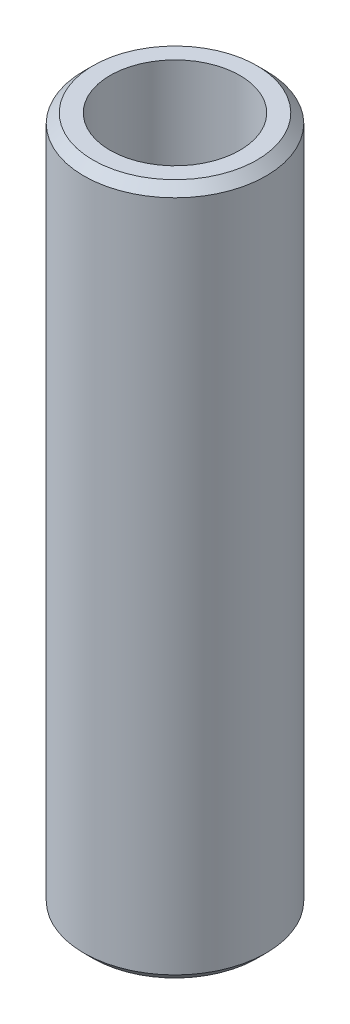
SolidWorks part; units mm, degrees
ref_plane "Front Plane" through (0, 0, 0) normal (0, 0, 1) x (1, 0, 0)
ref_plane "Top Plane" through (0, 0, 0) normal (0, 1, 0) x (1, 0, 0)
ref_plane "Right Plane" through (0, 0, 0) normal (1, 0, 0) x (0, 0, -1)
sketch "Sketch1" plane through (0, 0, 0) normal (0, 1, 0) x (1, 0, 0)
  circle A0 centre (0, 0) radius 47.5
  dimension "SHAFT_OD" = 95
extrude "Boss-Extrude1" add sketch "Sketch1" along normal blind 360.6354
sketch "Sketch2" plane through (0, 0, 0) normal (0, 1, 0) x (1, 0, 0)
  circle A0 centre (0, 0) radius 33.8481
  dimension "BORE_D" = 67.6961
extrude "Cut-Extrude1" cut sketch "Sketch2" along normal through all
chamfer "Chamfer1" distance 4.7891 angle 45 2 edges at (0, 360.6354, 47.5) (0, 0, 47.5)
